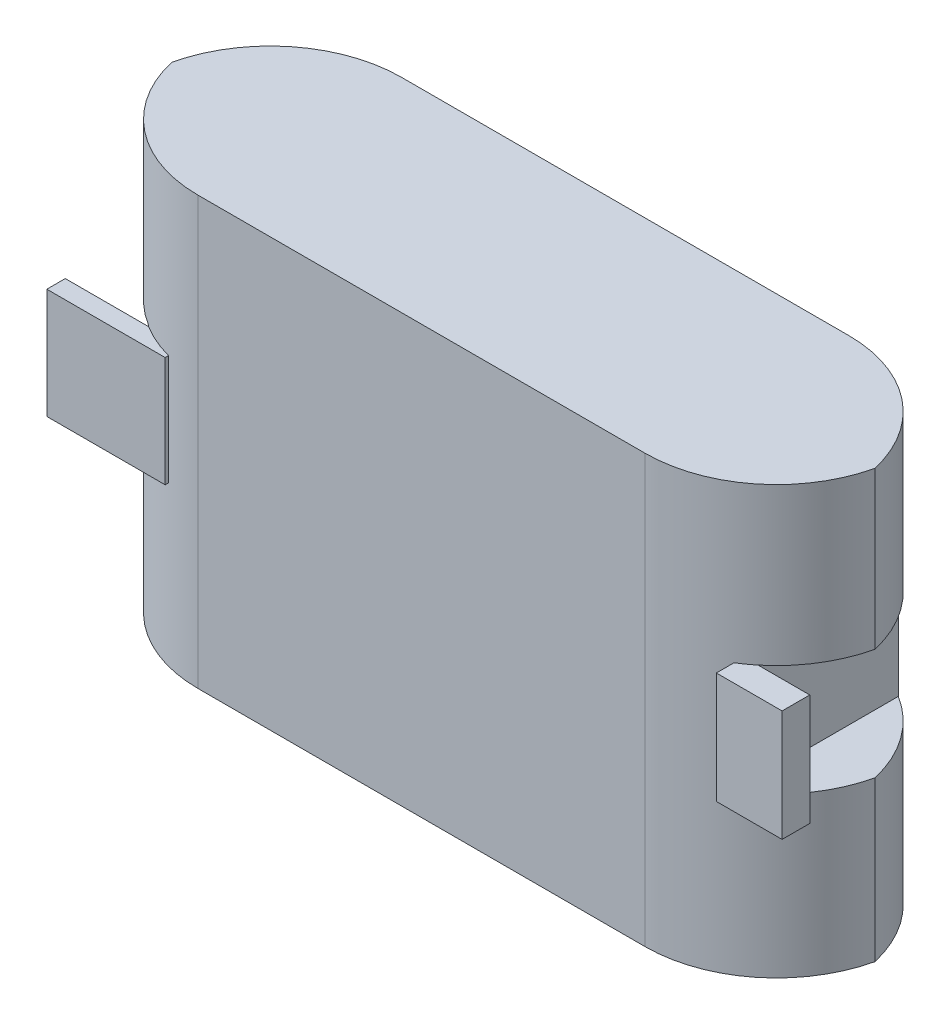
SolidWorks part; units mm, degrees
ref_plane "Front Plane" through (0, 0, 0) normal (0, 0, 1) x (1, 0, 0)
ref_plane "Top Plane" through (0, 0, 0) normal (0, 1, 0) x (1, 0, 0)
ref_plane "Right Plane" through (0, 0, 0) normal (1, 0, 0) x (0, 0, -1)
sketch "Sketch1" plane through (0, 0, 0) normal (0, 0, 1) x (1, 0, 0)
  line L1 (-46.5441, 36.7845) -> (61.4559, 36.7845)
  line L2 (-46.5441, 36.7845) -> (-46.5441, -28.2155)
  line L3 (-46.5441, -28.2155) -> (61.4559, -28.2155)
  line L4 (61.4559, 36.7845) -> (61.4559, -28.2155)
  dimension "D1" = 108
  dimension "D2" = 65
extrude "Boss-Extrude1" add sketch "Sketch1" along normal blind 31
fillet "Fillet1" radius 20 4 edges at (61.4559, 4.2845, 0) (61.4559, 4.2845, 31) (-46.5441, 4.2845, 31) (-46.5441, 4.2845, 0)
sketch "Sketch2" plane through (0, 0, 0) normal (0, 0, -1) x (-1, 0, 0)
  line L1 (-63.5325, 12.9387) -> (-51.9962, 12.9387)
  line L2 (-63.5325, 12.9387) -> (-63.5325, -3.9887)
  line L3 (-63.5325, -3.9887) -> (-51.9962, -3.9887)
  line L4 (-51.9962, 12.9387) -> (-51.9962, -3.9887)
  line L5 (57.965, 12.9387) -> (31.6964, 12.9387)
  line L6 (57.965, 12.9387) -> (57.965, -3.9887)
  line L7 (57.965, -3.9887) -> (31.6964, -3.9887)
  line L8 (31.6964, 12.9387) -> (31.6964, -3.9887)
extrude "Cut-Extrude1" cut sketch "Sketch2" against normal blind 28
sketch "Sketch3" plane through (-31.6964, 0, 0) normal (-1, 0, 0) x (0, 0, 1)
  line L1 (28.0271, 12.727) -> (30.8325, 12.727)
  line L2 (28.0271, 12.727) -> (28.0271, -4.0428)
  line L3 (28.0271, -4.0428) -> (30.8325, -4.0428)
  line L4 (30.8325, 12.727) -> (30.8325, -4.0428)
extrude "Boss-Extrude2" add sketch "Sketch3" along normal blind 18
sketch "Sketch4" plane through (51.9962, 0, 0) normal (1, 0, 0) x (0, 0, -1)
  line L0 (-27.9971, 12.9387) -> (-3.0029, 12.9387) construction
  line L1 (-26.4711, 12.9387) -> (-30.6782, 12.9387)
  line L2 (-26.4711, 12.9387) -> (-26.4711, -3.9887)
  line L3 (-26.4711, -3.9887) -> (-30.6782, -3.9887)
  line L4 (-30.6782, 12.9387) -> (-30.6782, -3.9887)
  line L5 (-27.9971, -3.9887) -> (-3.0029, -3.9887) construction
extrude "Boss-Extrude3" add sketch "Sketch4" along normal blind 10
